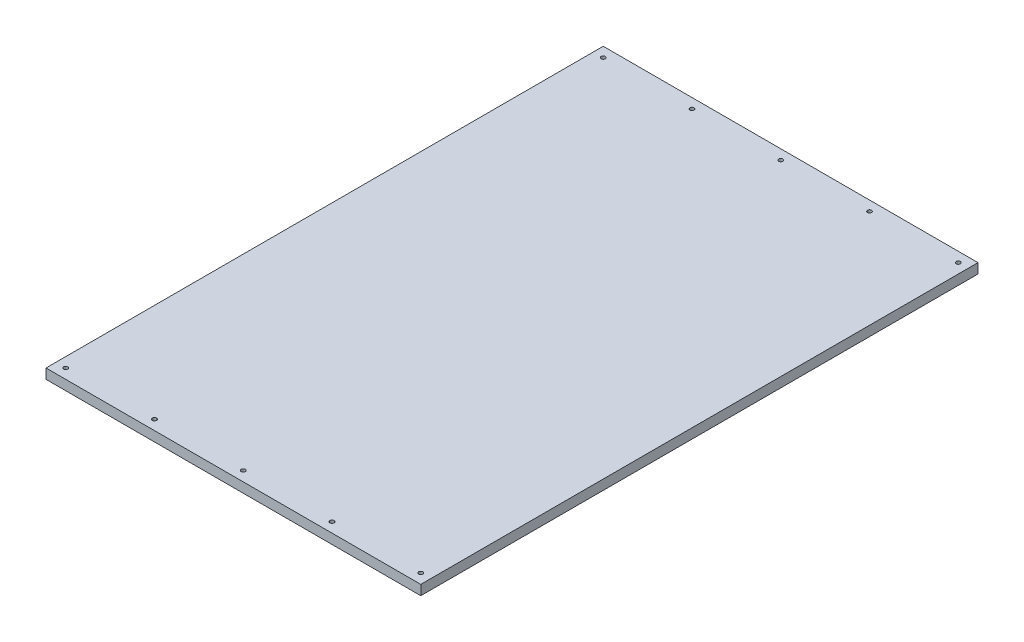
SolidWorks part; units mm, degrees
ref_plane "Front Plane" through (0, 0, 0) normal (0, 0, 1) x (1, 0, 0)
ref_plane "Top Plane" through (0, 0, 0) normal (0, 1, 0) x (1, 0, 0)
ref_plane "Right Plane" through (0, 0, 0) normal (1, 0, 0) x (0, 0, -1)
sketch "Sketch1" plane through (0, 0, 0) normal (0, 1, 0) x (1, 0, 0)
  line L1 (-190, 282.5) -> (190, 282.5)
  line L2 (-190, 282.5) -> (-190, -282.5)
  line L3 (-190, -282.5) -> (190, -282.5)
  line L4 (190, 282.5) -> (190, -282.5)
  line L5 (-190, 282.5) -> (190, -282.5) construction
  line L6 (-190, -282.5) -> (190, 282.5) construction
  point P0 (0, 0)
  dimension "D1" = 565
  dimension "D2" = 380
extrude "Boss-Extrude1" add sketch "Sketch1" along normal blind 10
sketch "Sketch2" plane through (0, 10, 0) normal (0, 1, 0) x (1, 0, 0)
  line L0 (-190, 282.5) -> (-190, 272.5) construction
  line L1 (-190, 282.5) -> (-190, -282.5) construction
  line L2 (-190, 272.5) -> (190, 272.5) construction
  line L3 (-5.5, 0) -> (5.5, 0) construction
  circle A0 centre (0, 272.5) radius 2.1
  circle A1 centre (90, 272.5) radius 2.1
  circle A2 centre (180, 272.5) radius 2.1
  circle A3 centre (-90, 272.5) radius 2.1
  circle A4 centre (-180, 272.5) radius 2.1
  circle A5 centre (180, -272.5) radius 2.1
  circle A6 centre (90, -272.5) radius 2.1
  circle A7 centre (0, -272.5) radius 2.1
  circle A8 centre (-90, -272.5) radius 2.1
  circle A9 centre (-180, -272.5) radius 2.1
  dimension "D3" = 4.2
  dimension "D4" = 4.2
  dimension "D5" = 4.2
  dimension "D6" = 4.2
  dimension "D7" = 4.2
  dimension "D1" = 10
  dimension "D2" = 380
  dimension "D8" = 10
  dimension "D9" = 90
  dimension "D10" = 10
  dimension "D11" = 90
extrude "Cut-Extrude1" cut sketch "Sketch2" against normal blind 10
